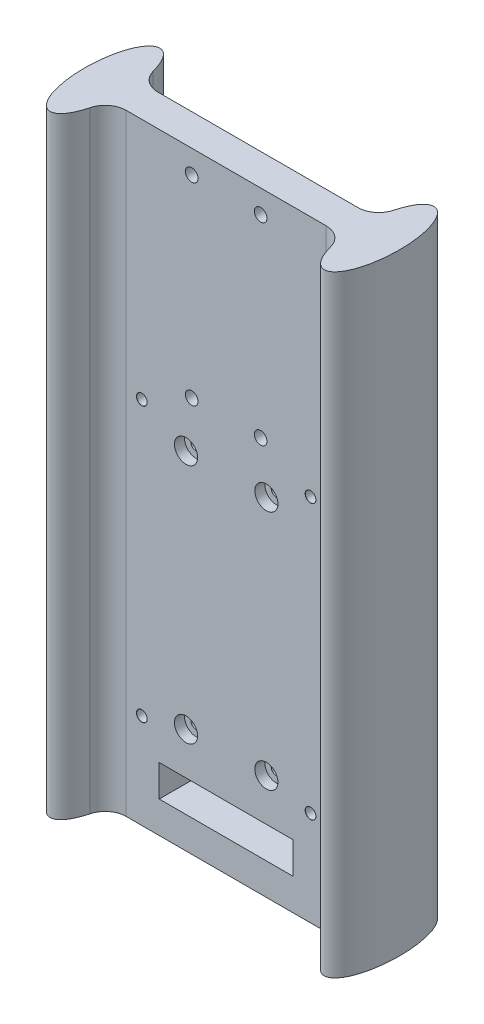
SolidWorks part; units mm, degrees
ref_plane "Front Plane" through (0, 0, 0) normal (0, 0, 1) x (1, 0, 0)
ref_plane "Top Plane" through (0, 0, 0) normal (0, 1, 0) x (1, 0, 0)
ref_plane "Right Plane" through (0, 0, 0) normal (1, 0, 0) x (0, 0, -1)
sketch "Sketch1" plane through (0, 0, 0) normal (0, 1, 0) x (1, 0, 0)
  line L0 (-32.5, 0) -> (-37.35, 0) construction
  line L1 (32.5, 3.75) -> (-32.5, 3.75)
  line L2 (32.5, 3.75) -> (32.5, -3.75)
  line L3 (32.5, -3.75) -> (-32.5, -3.75)
  line L4 (-32.5, 3.75) -> (-32.5, -3.75)
  line L5 (32.5, 3.75) -> (-32.5, -3.75) construction
  line L6 (32.5, -3.75) -> (-32.5, 3.75) construction
  line L7 (32.5, 0) -> (37.35, 0) construction
  ellipse E0 centre (-32.5, 0) end of major axis (-32.5, -13) minor radius 4.85
  ellipse E1 centre (32.5, 0) end of major axis (32.5, 13) minor radius 4.85
  point P0 (0, 0)
  dimension "D1" = 74.7
  dimension "D2" = 7.5
  dimension "D4" = 65
  dimension "D6" = 13
  dimension "D7" = 13
extrude "Boss-Extrude1" add sketch "Sketch1" along normal blind 145 contours E1 L1 E0 L3 | L3 E0 L1 L4 | L1 E0 L3 L4 | L1 E1 L3 L2 | L3 E1 L1 L2 region at (30.1087, 0, 0) region at (33.0287, 0, 0) region at (0, 0, 0) region at (-30.1087, 0, 0) region at (-33.0287, 0, 0)
fillet "Fillet1" radius 5 4 edges at (-27.8562, 72.5, -3.75) (27.8562, 72.5, -3.75) (27.8562, 72.5, 3.75) (-27.8562, 72.5, 3.75)
sketch "Sketch3" plane through (0, 0, -3.75) normal (0, 0, -1) x (-1, 0, 0)
  line L0 (0, 61.275) -> (0, 0) construction
  line L1 (15.875, 20) -> (-15.875, 20)
  line L2 (15.875, 20) -> (15.875, 102.55)
  line L3 (15.875, 102.55) -> (-15.875, 102.55)
  line L4 (-15.875, 20) -> (-15.875, 102.55)
  line L5 (15.875, 20) -> (-15.875, 102.55) construction
  line L6 (15.875, 102.55) -> (-15.875, 20) construction
  line L7 (23.6972, 0) -> (28.5334, 0) construction
  line L8 (-23.6972, 0) -> (23.6972, 0) construction
  line L9 (20.875, 102.55) -> (25.875, 102.55)
  line L10 (9.525, 25) -> (-9.525, 25)
  line L11 (9.525, 25) -> (9.525, 82.15)
  line L12 (9.525, 82.15) -> (-9.525, 82.15)
  line L13 (-9.525, 25) -> (-9.525, 82.15)
  line L14 (9.525, 25) -> (-9.525, 82.15) construction
  line L15 (9.525, 82.15) -> (-9.525, 25) construction
  line L16 (20.875, 102.55) -> (20.875, 20)
  line L17 (20.875, 20) -> (25.875, 20)
  line L18 (25.875, 102.55) -> (25.875, 20)
  line L19 (0, 53.575) -> (0, 20) construction
  line L20 (-15.875, 7.5) -> (15.875, 7.5)
  line L21 (-15.875, 7.5) -> (-15.875, 15)
  line L22 (-15.875, 15) -> (15.875, 15)
  line L23 (15.875, 7.5) -> (15.875, 15)
  point P0 (0, 61.275)
  dimension "D1" = 31.75
  dimension "D2" = 82.55
  dimension "D3" = 20
  dimension "D4" = 57.15
  dimension "D5" = 19.05
  dimension "D6" = 5
  dimension "D7" = 5
  dimension "D8" = 82.55
  dimension "D9" = 20
  dimension "D10" = 7.5
  dimension "D11" = 7.5
  dimension "D12" = 5
extrude "Cut-Extrude2" cut sketch "Sketch3" against normal through all both and the other way through all contours L21 L20 L23 L22
hole_wizard "Tap Drill for M3x0.5 Tap1" positions "3DSketch1" profile "Sketch4" hole size "M3x0.5" standard "ANSI Metric" end condition through all
sketch3d "3DSketch1"
  point P0 (9.525, 82.15, -3.75)
  point P3 (-9.525, 82.15, -3.75)
  point P6 (-9.525, 25, -3.75)
  point P9 (9.525, 25, -3.75)
sketch "Sketch4" plane through (9.525, 82.15, -3.75) normal (1, 0, 0) x (0, 1, 0)
  line L0 (0, 0) -> (0, 16.75)
  line L1 (0, 16.75) -> (1.25, 16.75)
  line L2 (1.25, 16.75) -> (1.25, 0)
  line L5 (1.25, 0) -> (0, 0)
  line L11 (0, -6.35) -> (0, 107.95) construction
  dimension "Thru Hole Dia." = 2.5
  dimension "Thru Hole Depth" = 16.75
sketch "Sketch5" plane through (0, 0, 3.75) normal (0, 0, 1) x (1, 0, 0)
  line L0 (-15.875, 15) -> (15.875, 15) construction
  line L1 (17.5, 25) -> (-17.5, 25)
  line L2 (17.5, 25) -> (17.5, 85)
  line L3 (17.5, 85) -> (-17.5, 85)
  line L4 (-17.5, 25) -> (-17.5, 85)
  line L5 (17.5, 25) -> (-17.5, 85) construction
  line L6 (17.5, 85) -> (-17.5, 25) construction
  line L7 (22.6, 19.9) -> (22.6, 90.1)
  line L8 (0, 15) -> (0, 55) construction
  line L9 (22.6, 90.1) -> (-22.6, 90.1)
  line L10 (-22.6, 19.9) -> (-22.6, 90.1)
  line L11 (22.6, 19.9) -> (-22.6, 19.9)
  line L12 (20, 22.5) -> (20, 87.5) construction
  line L13 (20, 87.5) -> (-20, 87.5) construction
  line L14 (-20, 22.5) -> (-20, 87.5) construction
  line L15 (20, 22.5) -> (-20, 22.5) construction
  point P0 (0, 55)
  dimension "D1" = 40
  dimension "D2" = 60
  dimension "D3" = 35
  dimension "D4" = 5.1
  dimension "D5" = 2.5
sketch "Sketch6" plane through (0, 0, 3.75) normal (0, 0, 1) x (1, 0, 0)
  circle A0 centre (9.525, 82.15) radius 2.75
  circle A1 centre (-9.525, 82.15) radius 2.75
  circle A2 centre (9.525, 25) radius 2.75
  circle A4 centre (-9.525, 25) radius 2.75
  dimension "D1" = 5.5
  dimension "D2" = 5.5
  dimension "D3" = 5.5
  dimension "D4" = 5.5
extrude "Cut-Extrude4" cut sketch "Sketch6" against normal blind 2.4
sketch "Sketch7" plane through (0, 0, 3.75) normal (0, 0, 1) x (1, 0, 0)
  point P0 (-20, 87.5)
  point P3 (20, 87.5)
  point P6 (20, 22.5)
  point P9 (-20, 22.5)
hole_wizard "Tap Drill for M3 Tap1" positions "Sketch7" profile "Sketch8" hole size "M3" standard "ISO" end condition through all
sketch "Sketch8" plane through (-20, 87.5, 3.75) normal (1, 0, 0) x (0, -1, 0)
  line L0 (0, 0) -> (0, 16.75)
  line L1 (0, 16.75) -> (1.25, 16.75)
  line L2 (1.25, 16.75) -> (1.25, 0.025)
  line L3 (1.25, 0.025) -> (1.275, 0)
  line L5 (1.275, 0) -> (0, 0)
  line L6 (-1.25, 0.025) -> (-1.275, 0) construction
  line L11 (0, -6.35) -> (0, 107.95) construction
  dimension "Thru Hole Dia." = 2.5
  dimension "Thru Hole Depth" = 16.75
  dimension "Near C'Sink Dia." = 2.55
  dimension "Near C'Sink Angle" = 90
sketch "Sketch9" plane through (0, 0, -3.75) normal (0, 0, -1) x (-1, 0, 0)
  line L0 (0, 0) -> (0, 145) construction
  line L1 (-23.6972, 0) -> (23.6972, 0) construction
  line L2 (-23.6972, 145) -> (23.6972, 145) construction
  line L3 (0, 116.6) -> (-10.668, 116.6) construction
  line L4 (10.668, 142) -> (-10.668, 142)
  line L5 (10.668, 142) -> (10.668, 91.2)
  line L6 (10.668, 91.2) -> (-10.668, 91.2)
  line L7 (-10.668, 142) -> (-10.668, 91.2)
  line L8 (10.668, 142) -> (-10.668, 91.2) construction
  line L9 (10.668, 91.2) -> (-10.668, 142) construction
  circle A0 centre (-8.168, 139.5) radius 1.5
  circle A1 centre (-8.168, 93.7) radius 1.5
  circle A2 centre (8.168, 93.7) radius 1.5
  circle A3 centre (8.168, 139.5) radius 1.5
  point P6 (0, 116.6)
  dimension "D4" = 3
  dimension "D6" = 2.5
  dimension "D1" = 21.336
  dimension "D2" = 50.8
  dimension "D3" = 3
  dimension "D5" = 2.5
extrude "Cut-Extrude5" cut sketch "Sketch9" against normal through all contours A0 | A3 | A2 | A1 region at (8.168, 139.5, -3.75) region at (8.168, 93.7, -3.75) region at (-8.168, 93.7, -3.75) region at (-8.168, 139.5, -3.75)
